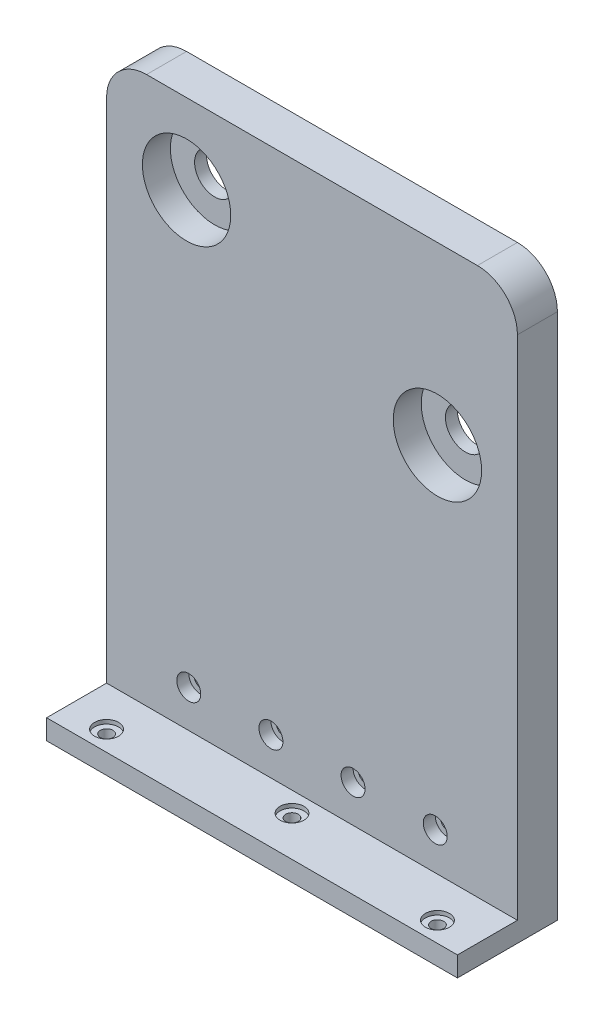
SolidWorks part; units mm, degrees
ref_plane "Front Plane" through (0, 0, 0) normal (0, 0, 1) x (1, 0, 0)
ref_plane "Top Plane" through (0, 0, 0) normal (0, 1, 0) x (1, 0, 0)
ref_plane "Right Plane" through (0, 0, 0) normal (1, 0, 0) x (0, 0, -1)
sketch "Sketch2" plane through (0, 0, 0) normal (0, 0, 1) x (1, 0, 0)
  line L1 (-10, 0) -> (-92.7384, 0)
  line L2 (0, -10) -> (0, -141.8022)
  line L3 (0, -141.8022) -> (-102.7384, -141.8022)
  line L4 (-102.7384, -10) -> (-102.7384, -141.8022)
  circle A0 centre (-82.7384, -20) radius 11.05
  circle A1 centre (-20, -43.8985) radius 11.05
  arc A2 (-10, 0) -> (0, -10) centre (-10, -10) cw
  arc A3 (-92.7384, 0) -> (-102.7384, -10) centre (-92.7384, -10) ccw
  circle A4 centre (-82.7384, -20) radius 5
  circle A5 centre (-20, -43.8985) radius 5
  point P11 (0, 0)
  dimension "D5" = 22.1
  dimension "D8" = 10
  dimension "D9" = 10
  dimension "D1" = 62.7384
  dimension "D2" = 20
  dimension "D3" = 20
  dimension "D4" = 20
  dimension "D6" = 97.9038
  dimension "D7" = 23.8985
extrude "Boss-Extrude2" add sketch "Sketch2" along normal blind 10 contours L1 A3 L4 L3 L2 A2 A0 A1 region at (-51.3692, -73.2874, 0)
extrude "Boss-Extrude3" add sketch "Sketch2<4>" along normal blind 3 contours A0 A4 | A1 A5 region at (-93.4759, -20, 0) region at (-30.7375, -43.8985, 0)
sketch "Sketch2<4>" plane through (0, 0, 0) normal (0, 0, 1) x (1, 0, 0) same geometry as "Sketch2"
sketch "Sketch4" plane through (0, 0, 10) normal (0, 0, 1) x (1, 0, 0)
  line L0 (-82.1908, -127.4522) -> (-61.6431, -127.4522) construction
  line L1 (-102.7384, -10) -> (-102.7384, -141.8022) construction
  line L2 (0, -141.8022) -> (-102.7384, -141.8022) construction
  circle A0 centre (-82.1908, -127.4522) radius 1.6
  circle A1 centre (-61.6431, -127.4522) radius 1.6
  circle A2 centre (-41.0954, -127.4522) radius 1.6
  circle A3 centre (-20.5477, -127.4522) radius 1.6
  circle A4 centre (-82.1908, -127.4522) radius 3
  circle A5 centre (-61.6431, -127.4522) radius 3
  circle A6 centre (-41.0954, -127.4522) radius 3
  circle A7 centre (-20.5477, -127.4522) radius 3
  dimension "D1" = 3.2
  dimension "D4" = 20.5477
  dimension "D5" = 14.35
  dimension "D6" = 6
  dimension "D3" = 20.5477
  dimension "D2" = 4
extrude "Cut-Extrude3" cut sketch "Sketch4" against normal blind 10 contours A1 | A2 | A3 | A0
extrude "Cut-Extrude4" cut sketch "Sketch4<5>" against normal blind 3
sketch "Sketch4<5>" plane through (0, 0, 10) normal (0, 0, 1) x (1, 0, 0) same geometry as "Sketch4"
sketch "Sketch5" plane through (0, 0, 0) normal (0, 0, -1) x (-1, 0, 0)
  line L1 (5.2942, -116.8272) -> (97.4442, -116.8272)
  line L2 (5.2942, -116.8272) -> (5.2942, -137.9772)
  line L3 (5.2942, -137.9772) -> (97.4442, -137.9772)
  line L4 (97.4442, -116.8272) -> (97.4442, -137.9772)
  line L6 (0, -141.8022) -> (102.7384, -141.8022) construction
  line L7 (7.3942, -118.9272) -> (95.3442, -118.9272)
  line L8 (7.3942, -118.9272) -> (7.3942, -135.8772)
  line L9 (7.3942, -135.8772) -> (95.3442, -135.8772)
  line L10 (95.3442, -118.9272) -> (95.3442, -135.8772)
  line L11 (102.7384, -10) -> (102.7384, -141.8022) construction
  line L12 (0, -141.8022) -> (102.7384, -141.8022)
  line L13 (0, -141.8022) -> (0, -113.0022)
  line L14 (0, -113.0022) -> (102.7384, -113.0022)
  line L15 (102.7384, -141.8022) -> (102.7384, -113.0022)
  point P4 (51.3692, -137.9772)
  point P7 (51.3692, -141.8022)
  point P11 (5.2942, -127.4022)
  point P20 (0, -127.4022)
  dimension "D1" = 21.15
  dimension "D2" = 92.15
  dimension "D3" = 2.1
  dimension "D4" = 2.1
  dimension "D5" = 2.1
  dimension "D6" = 2.1
  dimension "D7" = 28.8
extrude "Cut-Extrude5" cut sketch "Sketch5" against normal blind 3 contours L4 L1 L2 L3 L7 L10 L9 L8 region at (-51.3692, -117.7727, 0)
sketch "Sketch6" plane through (0, -141.8022, 0) normal (0, -1, 0) x (1, 0, 0)
  line L0 (0, 10) -> (0, 0) construction
  line L1 (-102.7384, 0) -> (0, 0)
  line L2 (-102.7384, 0) -> (-102.7384, 25)
  line L3 (-102.7384, 25) -> (0, 25)
  line L4 (0, 0) -> (0, 25)
  dimension "D1" = 25
extrude "Boss-Extrude4" add sketch "Sketch6" against normal blind 5
sketch "Sketch7" plane through (0, -136.8022, 0) normal (0, 1, 0) x (1, 0, 0)
  line L0 (-102.7384, -25) -> (-102.7384, -10) construction
  line L1 (0, -10) -> (0, -25) construction
  line L2 (0, -25) -> (-102.7384, -25) construction
  line L3 (0, -10) -> (-102.7384, -10) construction
  circle A0 centre (-92.7384, -20) radius 1.575
  circle A1 centre (-51.3692, -15) radius 1.575
  circle A2 centre (-10, -20) radius 1.575
  circle A3 centre (-92.7384, -20) radius 3
  circle A4 centre (-51.3692, -15) radius 3
  circle A5 centre (-10, -20) radius 3
  point P19 (-51.3692, -25)
  dimension "D1" = 3.15
  dimension "D2" = 6
  dimension "D3" = 10
  dimension "D4" = 10
  dimension "D5" = 5
  dimension "D6" = 5
extrude "Cut-Extrude6" cut sketch "Sketch7" against normal blind 5 contours A1 | A2 | A0
extrude "Cut-Extrude7" cut sketch "Sketch7<3>" against normal blind 1
sketch "Sketch7<3>" plane through (0, -136.8022, 0) normal (0, 1, 0) x (1, 0, 0) same geometry as "Sketch7"
